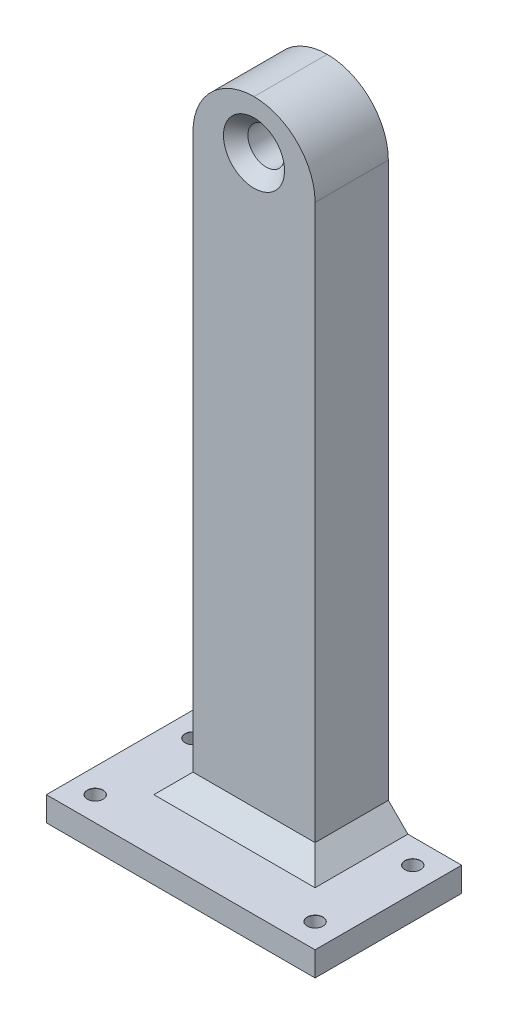
SolidWorks part; units mm, degrees
ref_plane "Front Plane" through (0, 0, 0) normal (0, 0, 1) x (1, 0, 0)
ref_plane "Top Plane" through (0, 0, 0) normal (0, 1, 0) x (1, 0, 0)
ref_plane "Right Plane" through (0, 0, 0) normal (1, 0, 0) x (0, 0, -1)
sketch "Sketch1" plane through (0, 0, 0) normal (0, 0, 1) x (1, 0, 0)
  line L0 (0, 0) -> (-12.5, 0)
  line L1 (-12.5, 0) -> (-12.5, 135)
  line L3 (12.5, 135) -> (12.5, 0)
  line L4 (12.5, 0) -> (0, 0)
  line L5 (0, 0) -> (0, 125) construction
  line L8 (-12.5, 135) -> (12.5, 135)
  circle A1 centre (0, 125) radius 3.75
  dimension "D5" = 7.5
  dimension "D1" = 25
  dimension "D2" = 125
  dimension "D3" = 10
extrude "Boss-Extrude1" add sketch "Sketch1" along normal blind 15
sketch "Sketch2" plane through (0, 0, 0) normal (0, 0, -1) x (-1, 0, 0)
  line L0 (-27.5, 5) -> (27.5, 5)
  line L4 (-27.5, 0) -> (-27.5, 5)
  line L8 (27.5, 0) -> (27.5, 5)
  line L9 (27.5, 0) -> (-27.5, 0)
  line L10 (12.5, 135) -> (12.5, 0) construction
  point P0 (0, 0)
  dimension "D1" = 15
  dimension "D2" = 5
extrude "Boss-Extrude2" add sketch "Sketch2" against normal blind 30
sketch "Sketch5" plane through (0, 5, 0) normal (0, 1, 0) x (1, 0, 0)
  line L0 (-27.5, 0) -> (-12.5, 0) construction
  line L1 (-27.5, -30) -> (27.5, -30) construction
  line L2 (-27.5, -30) -> (-27.5, 0) construction
  line L3 (27.5, -30) -> (27.5, 0) construction
  point P0 (-22.5, -5)
  point P2 (-22.5, -25)
  point P4 (22.5, -25)
  point P6 (22.5, -5)
  point P15 (0, 0)
  point P16 (0, 0)
  point P17 (0, 0)
  point P18 (0, 0)
  dimension "D1" = 5
  dimension "D2" = 5
  dimension "D3" = 5
  dimension "D4" = 5
hole_wizard "Ø3.2 (3.2) Diameter Hole1" positions "Sketch5" profile "Sketch4" hole size "Ø3.2" standard "ANSI Metric" end condition through all
sketch "Sketch4" plane through (-22.5, 5, 5) normal (1, 0, 0) x (0, 0, 1)
  line L0 (0, 0) -> (0, 5)
  line L1 (0, 5) -> (1.6, 5)
  line L2 (1.6, 5) -> (1.6, 0.025)
  line L3 (1.6, 0.025) -> (1.625, 0)
  line L5 (1.625, 0) -> (0, 0)
  line L6 (-1.6, 0.025) -> (-1.625, 0) construction
  line L11 (0, -6.35) -> (0, 107.95) construction
  dimension "Thru Hole Dia." = 3.2
  dimension "Thru Hole Depth" = 5
  dimension "Near C'Sink Dia." = 3.25
  dimension "Near C'Sink Angle" = 90
chamfer "Chamfer1" distance 4 angle 45 3 edges at (12.5, 5, 7.5) (-12.5, 5, 7.5) (0, 5, 15)
fillet "Fillet2" radius 12.5 2 edges at (12.5, 135, 7.5) (-12.5, 135, 7.5)
chamfer "Chamfer2" distance 2.5 angle 45 1 edges at (3.75, 125, 15)
